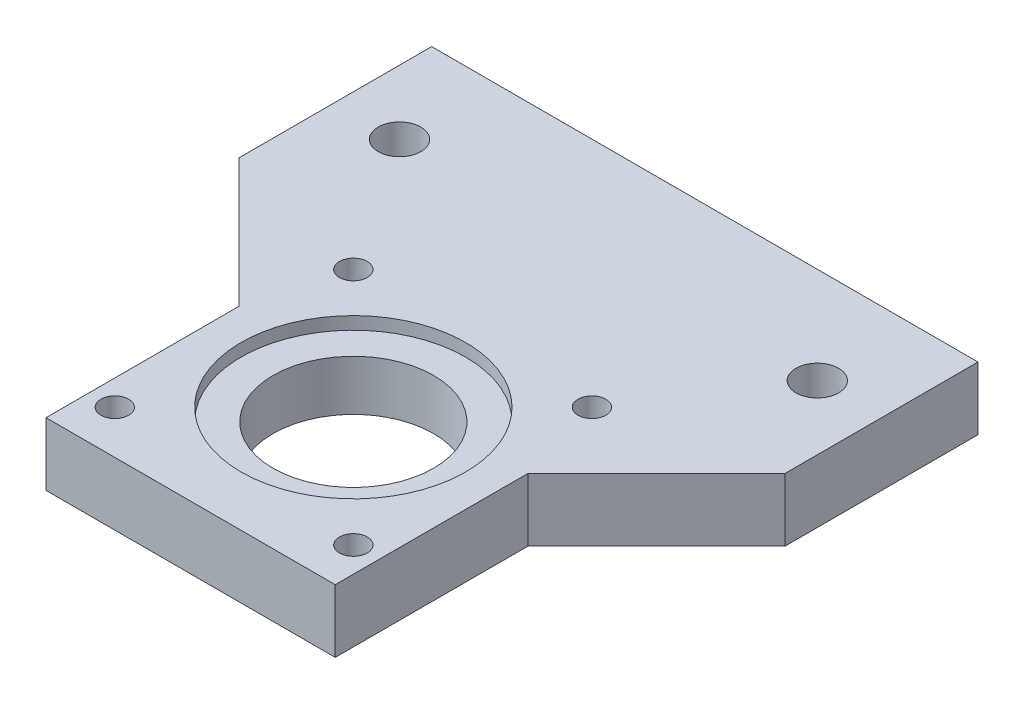
SolidWorks part; units mm, degrees
material "ASTM A36 Steel"
ref_plane "Front Plane" through (0, 0, 0) normal (0, 0, 1) x (1, 0, 0)
ref_plane "Top Plane" through (0, 0, 0) normal (0, 1, 0) x (1, 0, 0)
ref_plane "Right Plane" through (0, 0, 0) normal (1, 0, 0) x (0, 0, -1)
sketch "Sketch1" plane through (0, 0, 0) normal (0, 1, 0) x (1, 0, 0)
  line L0 (-28.575, 50.8) -> (-53.975, 50.8)
  line L1 (-28.575, 50.8) -> (28.575, 50.8)
  line L2 (-28.575, 50.8) -> (-28.575, -50.8) construction
  line L3 (-28.575, -50.8) -> (28.575, -50.8)
  line L4 (28.575, 50.8) -> (28.575, -50.8) construction
  line L5 (-28.575, 50.8) -> (28.575, -50.8) construction
  line L6 (-28.575, -50.8) -> (28.575, 50.8) construction
  line L7 (-53.975, 50.8) -> (-53.975, 12.7)
  line L8 (-53.975, 12.7) -> (-28.575, -12.7)
  line L9 (-28.575, -12.7) -> (-28.575, -50.8)
  line L10 (0, -50.8) -> (0, 50.8) construction
  line L11 (53.975, 12.7) -> (28.575, -12.7)
  line L12 (53.975, 50.8) -> (53.975, 12.7)
  line L13 (28.575, 50.8) -> (53.975, 50.8)
  line L14 (28.575, -12.7) -> (28.575, -50.8)
  point P0 (0, 0)
  dimension "D1" = 57.15
  dimension "D2" = 101.6
  dimension "D3" = 45
  dimension "D4" = 38.1
  dimension "D5" = 25.4
extrude "Boss-Extrude1" add sketch "Sketch1" along normal mid plane 15.875
hole_wizard "5/16 Clearance Hole1" positions "Sketch2" profile "Sketch3" hole size "5/16" standard "ANSI Inch" end condition through all
sketch "Sketch2" plane through (0, 7.9375, 0) normal (0, 1, 0) x (1, 0, 0)
  line L0 (53.975, 50.8) -> (-53.975, 50.8) construction
  line L2 (41.275, 31.75) -> (53.975, 31.75) construction
  line L5 (-41.275, 31.75) -> (-53.975, 31.75) construction
  line L9 (53.975, 12.7) -> (53.975, 50.8) construction
  line L10 (-53.975, 50.8) -> (-53.975, 12.7) construction
  point P0 (-41.275, 31.75)
  point P2 (41.275, 31.75)
  point P21 (0, 0)
  point P24 (0, 0)
  dimension "D1" = 19.05
  dimension "D2" = 12.7
sketch "Sketch3" plane through (-41.275, 7.9375, -31.75) normal (1, 0, 0) x (0, 0, 1)
  line L0 (0, 0) -> (0, 15.875)
  line L1 (0, 15.875) -> (4.2164, 15.875)
  line L2 (4.2164, 15.875) -> (4.2164, 0)
  line L5 (4.2164, 0) -> (0, 0)
  line L11 (0, -6.35) -> (0, 107.95) construction
  dimension "Thru Hole Dia." = 8.4328
  dimension "Thru Hole Depth" = 15.875
sketch "Sketch4" plane through (0, 7.9375, 0) normal (0, 1, 0) x (1, 0, 0)
  line L22 (28.575, -50.8) -> (28.575, -12.7)
  line L23 (28.575, -12.7) -> (53.975, 12.7)
  line L24 (53.975, 12.7) -> (53.975, 50.8)
  line L25 (53.975, 50.8) -> (-53.975, 50.8)
  line L26 (-53.975, 50.8) -> (-53.975, 12.7)
  line L27 (-53.975, 12.7) -> (-28.575, -12.7)
  line L28 (-28.575, -12.7) -> (-28.575, -50.8)
  line L29 (-28.575, -50.8) -> (28.575, -50.8)
  line L30 (28.575, -50.8) -> (28.575, -12.7)
  line L31 (28.575, -12.7) -> (53.975, 12.7)
  line L32 (53.975, 12.7) -> (53.975, 50.8)
  line L33 (53.975, 50.8) -> (-53.975, 50.8)
  line L34 (-53.975, 50.8) -> (-53.975, 12.7)
  line L35 (-53.975, 12.7) -> (-28.575, -12.7)
  line L36 (-28.575, -12.7) -> (-28.575, -50.8)
  line L37 (-28.575, -50.8) -> (28.575, -50.8)
  dimension "D1" = 0
extrude "Cut-Extrude1" cut sketch "Sketch4" against normal up to surface (3.425 mm away)
hole_wizard "M5 Clearance Hole1" positions "Sketch5" profile "Sketch6" hole size "M5" standard "ANSI Metric" end condition through all
sketch "Sketch5" plane through (0, 4.5125, 0) normal (0, 1, 0) x (1, 0, 0)
  point P0 (23.57, -42.22)
  point P3 (-23.57, -42.22)
  point P6 (-23.57, 4.92)
  point P9 (23.57, 4.92)
sketch "Sketch6" plane through (23.57, 4.5125, 42.22) normal (1, 0, 0) x (0, 0, 1)
  line L0 (0, 0) -> (0, 12.45)
  line L1 (0, 12.45) -> (2.75, 12.45)
  line L2 (2.75, 12.45) -> (2.75, 0)
  line L5 (2.75, 0) -> (0, 0)
  line L11 (0, -6.35) -> (0, 107.95) construction
  dimension "Thru Hole Dia." = 5.5
  dimension "Thru Hole Depth" = 12.45
sketch "Sketch8" plane through (0, 4.5125, 0) normal (0, 1, 0) x (1, 0, 0)
  circle A0 centre (0, -18.65) radius 19 construction
  circle A1 centre (0, -18.65) radius 19 construction
  circle A4 centre (0, -18.65) radius 22.175
  circle A5 centre (0, -18.65) radius 22.175
  dimension "D1" = 3.175
extrude "Cut-Extrude3" cut sketch "Sketch8" against normal offset from surface (2.5 mm away) 1 offset beyond the face yes
sketch "Sketch9" plane through (0, 2.0125, 0) normal (0, 1, 0) x (1, 0, 0)
  circle A0 centre (0, -18.65) radius 15.875
  circle A1 centre (0, -18.65) radius 22.175
  circle A2 centre (0, -18.65) radius 22.175 construction
  dimension "D2" = 31.75
  dimension "D1" = 0
extrude "Cut-Extrude4" cut sketch "Sketch9" against normal through all
